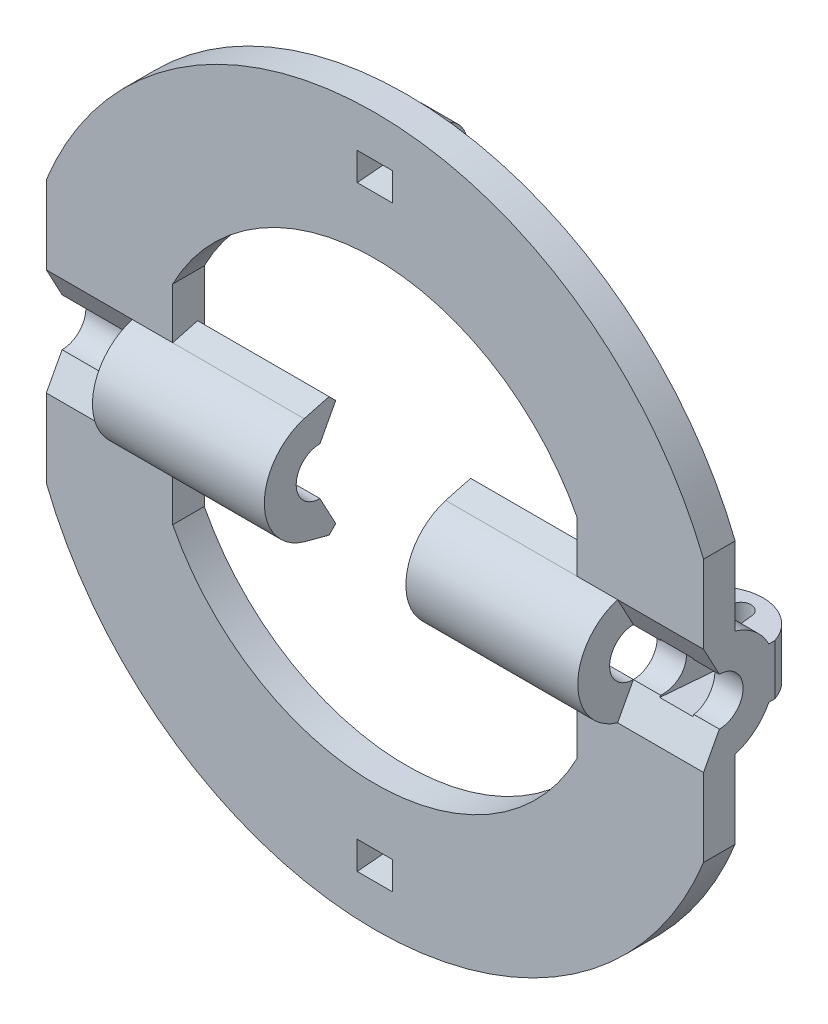
SolidWorks part; units mm, degrees
ref_plane "Front Plane" through (0, 0, 0) normal (0, 0, 1) x (1, 0, 0)
ref_plane "Top Plane" through (0, 0, 0) normal (0, 1, 0) x (1, 0, 0)
ref_plane "Right Plane" through (0, 0, 0) normal (1, 0, 0) x (0, 0, -1)
sketch "Sketch1" plane through (0, 0, 0) normal (0, 0, 1) x (1, 0, 0)
  circle A0 centre (0, 0) radius 17.78
  circle A1 centre (0, 0) radius 11.43
  dimension "D1" = 35.56
  dimension "D2" = 22.86
extrude "Boss-Extrude1" add sketch "Sketch1" along normal blind 0.7937 and the other way blind 0.7937
ref_plane "Plane1" through (10.16, 0, 0) normal (1, 0, 0) x (0, 0, -1)
sketch "Sketch20" plane through (10.16, 0, 0) normal (1, 0, 0) x (0, 0, -1)
  circle A0 centre (0, 0) radius 2.794
  dimension "D1" = 5.588
extrude "Boss-Extrude7" add sketch "Sketch20" along normal blind 6.35
sketch "Sketch21" plane through (0, 0, 0.7937) normal (0, 0, 1) x (1, 0, 0)
  line L0 (16.51, 0) -> (16.51, 6.5991)
  line L1 (16.51, -2.6789) -> (16.51, 2.6789) construction
  line L2 (16.51, 6.5991) -> (17.78, 6.5991)
  line L3 (17.78, 6.5991) -> (17.78, 0)
  line L4 (17.78, 0) -> (17.78, -6.5991)
  line L5 (16.51, 0) -> (16.51, -6.5991)
  line L6 (16.51, -6.5991) -> (17.78, -6.5991)
  circle A0 centre (0, 0) radius 17.78 construction
extrude "cut for screw clearance on side" cut sketch "Sketch21" against normal through all
mirror "Mirror1" about plane through (0, 0, 0) normal (1, 0, 0) of "cut for screw clearance on side", "Boss-Extrude7"
sketch "Sketch22" plane through (10.16, 0, 0) normal (1, 0, 0) x (0, 0, -1)
  circle A0 centre (0, 0) radius 1.1938
  dimension "D1" = 2.3876
extrude "cut for axle" cut sketch "Sketch22" against normal through all and the other way through all
sketch "Sketch35" plane through (10.16, 0, 0) normal (-1, 0, 0) x (0, 0, 1)
  line L6 (0, 1.1938) -> (-0.7937, 2.6789)
  line L7 (-0.7937, 2.6789) -> (-3.0886, 2.6789)
  line L8 (-3.0886, 2.6789) -> (-3.0886, -2.6789)
  line L9 (-3.0886, -2.6789) -> (-0.7937, -2.6789)
  line L10 (-0.7937, -2.6789) -> (0, -1.1938)
  arc A0 (0, 1.1938) -> (0, -1.1938) centre (0, 0) cw
  circle A2 centre (0, 0) radius 1.1938 construction
extrude "cut1 for straight pull on axle hole" cut sketch "Sketch35" against normal blind 2.032
sketch "Sketch41" plane through (12.192, 0, 0) normal (-1, 0, 0) x (0, 0, 1)
  line L0 (0, 1.1938) -> (0.7937, 2.6789)
  line L1 (0, 1.1938) -> (-0.7937, 2.6789) construction
  line L2 (0.7937, 2.6789) -> (3.1585, 2.8858)
  line L3 (3.1585, 2.8858) -> (3.1585, -2.8858)
  line L4 (3.1585, -2.8858) -> (0.7937, -2.6789)
  line L5 (0.7937, -11.43) -> (0.7937, -2.6789) construction
  line L6 (0.7937, -2.6789) -> (0, -1.1938)
  line L7 (0.7937, -2.6789) -> (3.857, -2.6789) construction
  line L8 (0.7937, 2.6789) -> (3.857, 2.6789) construction
  arc A1 (0, -1.1938) -> (0, 1.1938) centre (0, 0) ccw construction
  arc A2 (-0.7937, -2.6789) -> (0.7937, -2.6789) centre (0, 0) ccw construction
  arc A3 (0, 1.1938) -> (0, -1.1938) centre (0, 0) ccw
  dimension "D1" = 5
  dimension "D2" = 5
extrude "cut2 for straight pull on axle hole" cut sketch "Sketch41" against normal through all
sketch "Sketch42" plane through (0, 0, 0) normal (0, 1, 0) x (1, 0, 0)
  line L2 (12.192, 2.794) -> (12.192, 0.7937) construction
  line L3 (16.51, 0.7938) -> (16.51, 2.794) construction
  line L4 (12.192, 2.794) -> (12.192, 2.3925)
  line L5 (12.192, 2.3925) -> (16.51, 2.3925)
  line L6 (16.51, 2.3925) -> (16.51, 2.794)
  circle A0 centre (14.351, 3.2422) radius 0.508
  arc A1 (12.192, 2.794) -> (16.51, 2.794) centre (14.351, 2.0759) cw
  dimension "D1" = 1.016
extrude "x axis ring" add sketch "Sketch42" along normal blind 1.27 and the other way blind 1.27
sketch "Sketch43" plane through (0, 1.27, 0) normal (0, 1, 0) x (1, 0, 0)
  line L0 (13.843, 3.2422) -> (13.4899, -0.7937)
  line L1 (-16.51, -0.7937) -> (16.51, -0.7937) construction
  line L2 (13.4899, -0.7937) -> (15.3159, -0.7937)
  line L3 (15.3159, -0.7937) -> (14.859, 3.2422)
  line L4 (13.843, 3.2422) -> (13.843, -1.0687) construction
  line L5 (14.859, 3.2422) -> (14.859, -1.0687) construction
  circle A0 centre (14.351, 3.2422) radius 0.508 construction
  arc A1 (13.843, 3.2422) -> (14.859, 3.2422) centre (14.351, 3.2422) cw
  dimension "D1" = 5
extrude "cut for straight pull on x axis ring" cut sketch "Sketch43" against normal blind 2.54
sketch "Sketch29" plane through (0, 0, 0) normal (1, 0, 0) x (0, 0, -1)
  line L0 (0, 0) -> (7.245, 0) construction
  line L2 (0.8034, 0) -> (0.7938, 16.51) construction
  line L3 (0.7938, 6.5991) -> (0.7937, 17.78) construction
  line L4 (0.7938, 16.51) -> (1.4288, 16.51)
  line L5 (1.4288, 16.51) -> (1.4288, 14.986) construction
  line L6 (0.7955, 13.462) -> (1.4288, 13.462)
  line L7 (1.4288, 13.462) -> (1.4288, 14.986) construction
  line L8 (0.7938, 16.51) -> (0.7955, 13.462)
  circle A0 centre (1.4288, 14.986) radius 0.508
  arc A1 (1.4288, 16.51) -> (1.4288, 13.462) centre (1.4288, 14.986) cw
  dimension "D4" = 1.016
  dimension "D1" = 16.51
  dimension "D2" = 0.635
  dimension "D3" = 1.524
  dimension "D5" = 1.524
extrude "y axis control wire ring" add sketch "Sketch29" along normal blind 0.889 and the other way blind 0.889 separate body
sketch "Sketch30" plane through (0.889, 0, 0) normal (1, 0, 0) x (0, 0, -1)
  line L0 (1.4288, 15.494) -> (-0.7938, 15.494) construction
  line L1 (-0.7937, 17.78) -> (-0.7937, 6.5991) construction
  line L2 (1.4288, 14.478) -> (-0.7938, 14.478) construction
  line L3 (1.4288, 15.494) -> (-0.7937, 15.6884)
  line L4 (1.4288, 14.478) -> (-0.7937, 14.2836)
  line L5 (-0.7937, 15.6884) -> (-0.7937, 14.2836)
  circle A0 centre (1.4288, 14.986) radius 0.508 construction
  arc A1 (1.4288, 15.494) -> (1.4288, 14.478) centre (1.4288, 14.986) cw
  dimension "D1" = 5
  dimension "D2" = 5
extrude "y axis straight pull feature" cut sketch "Sketch30" against normal blind 1.778
mirror "mirror of y ring" about plane through (0, 0, 0) normal (0, 1, 0) of bodies 119
sketch "Sketch31" plane through (0.889, 0, 0) normal (1, 0, 0) x (0, 0, -1)
  line L0 (1.4288, -14.478) -> (-0.7938, -14.478) construction
  line L1 (-0.7937, -6.5991) -> (-0.7937, -17.78) construction
  line L2 (1.4288, -15.494) -> (-0.7937, -15.494) construction
  line L3 (1.4288, -14.478) -> (-0.7937, -14.2836)
  line L4 (1.4288, -15.494) -> (-0.7937, -15.6884)
  line L5 (-0.7937, -14.2836) -> (-0.7937, -15.6884)
  arc A0 (1.4288, -14.478) -> (1.4288, -15.494) centre (1.4288, -14.986) cw
  dimension "D1" = 5
  dimension "D2" = 5
extrude "y axis straight pull feature on mirrorr" cut sketch "Sketch31" against normal blind 1.778
sketch "Sketch40" plane through (0, 0, 0.7937) normal (0, 0, 1) x (1, 0, 0)
  line L0 (10.16, 5.2498) -> (10.16, 2.6789)
  line L1 (10.16, -3.9299) -> (10.16, 3.9299) construction
  line L3 (10.16, 2.6789) -> (11.1116, 2.6789)
  line L4 (10.16, 5.2498) -> (10.7369, 4.3721)
  line L5 (10.7369, 4.3721) -> (11.1116, 2.6789)
extrude "build out material for axle hole" add sketch "Sketch40" against normal blind 1.5875
mirror "Mirror16" about plane through (0, 0, 0) normal (0, 1, 0) of "build out material for axle hole"
mirror "Mirror17" about plane through (0, 0, 0) normal (1, 0, 0) of "Mirror16", "build out material for axle hole"
sketch "Sketch44" plane through (-10.16, 0, 0) normal (1, 0, 0) x (0, 0, -1)
  line L0 (0, 1.1938) -> (0.7937, 2.6789)
  line L1 (0.7937, 5.2363) -> (0.7937, 2.6789) construction
  line L3 (0.7937, 2.6789) -> (4.7459, 2.6789)
  line L4 (0, -1.1938) -> (0.7937, -2.6789)
  line L5 (0.7937, -2.6789) -> (4.7459, -2.6789)
  line L6 (4.7459, -2.6789) -> (4.7459, 2.6789)
  circle A2 centre (0, 0) radius 1.1938 construction
  arc A3 (0.7937, -2.6789) -> (0.7937, 2.6789) centre (0, 0) ccw construction
  arc A4 (0, 1.1938) -> (0, -1.1938) centre (0, 0) ccw
extrude "Cut-Extrude1" cut sketch "Sketch44" against normal blind 2.032
sketch "Sketch45" plane through (-12.192, 0, 0) normal (1, 0, 0) x (0, 0, -1)
  line L0 (0, 1.1938) -> (-0.7937, 2.6789)
  line L1 (0.7937, 2.6789) -> (0, 1.1938) construction
  line L2 (-0.7937, 2.6789) -> (-3.1365, 2.6789)
  line L3 (-3.1365, 2.6789) -> (-3.1365, -2.6789)
  line L4 (-3.1365, -2.6789) -> (-0.7937, -2.6789)
  line L5 (-0.7937, -2.6789) -> (0, -1.1938)
  arc A0 (0, -1.1938) -> (0, 1.1938) centre (0, 0) ccw construction
  arc A1 (0, 1.1938) -> (0, -1.1938) centre (0, 0) cw
extrude "Cut-Extrude2" cut sketch "Sketch45" against normal through all
sketch "Sketch46" plane through (-10.16, 0, 0) normal (1, 0, 0) x (0, 0, -1)
  line L0 (0.7937, 2.6789) -> (0.4583, 3.0144)
  line L2 (0, -1.1938) -> (0.7937, -2.6789)
  line L4 (0.7937, 2.6789) -> (0, 1.1938)
  line L5 (0.4583, 3.0144) -> (-0.7937, 2.6789)
  line L7 (0.7937, 5.2363) -> (0.7937, 2.6789) construction
  line L9 (-0.7937, 5.2363) -> (-0.7937, 2.6789) construction
  line L12 (0.7937, -2.6789) -> (0.4583, -3.0144)
  line L13 (0.4583, -3.0144) -> (-0.7937, -2.6789)
  line L14 (0.7937, -5.2363) -> (0.7937, -2.6789) construction
  line L17 (-0.7937, -5.2363) -> (-0.7937, -2.6789) construction
  arc A1 (-0.7937, 2.6789) -> (-0.7937, -2.6789) centre (0, 0) ccw
  arc A2 (0, 1.1938) -> (0, -1.1938) centre (0, 0) ccw
  arc A4 (0, 1.1938) -> (0, -1.1938) centre (0, 0) ccw construction
  dimension "D1" = 45
  dimension "D2" = 75
  dimension "D3" = 45
  dimension "D4" = 75
extrude "Boss-Extrude8" add sketch "Sketch46" along normal blind 6.604
mirror "Mirror19" about plane through (0, 0, 0) normal (1, 0, 0) of "Boss-Extrude8"
